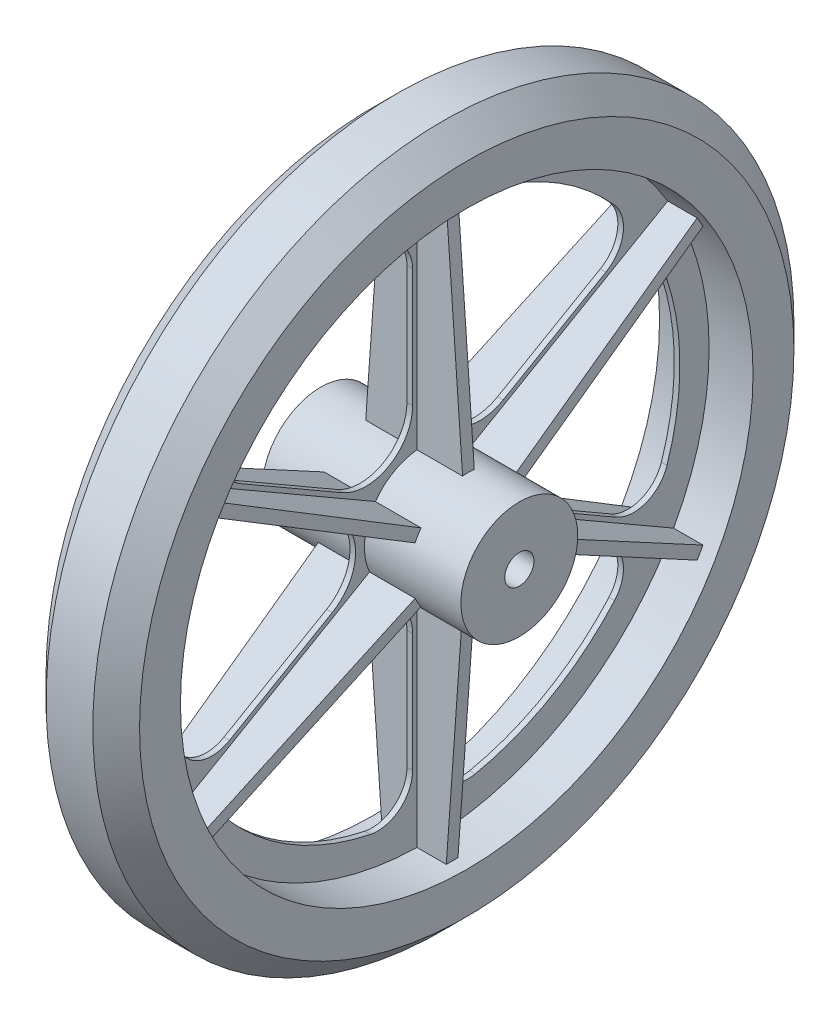
SolidWorks part; units mm, degrees
material "aluminio"
ref_plane "Alzado" through (0, 0, 0) normal (0, 0, 1) x (1, 0, 0)
ref_plane "Planta" through (0, 0, 0) normal (0, 1, 0) x (1, 0, 0)
ref_plane "Vista lateral" through (0, 0, 0) normal (1, 0, 0) x (0, 0, -1)
sketch "Croquis5" plane through (0, 0, 0) normal (1, 0, 0) x (0, 0, -1)
  circle A0 centre (0, 0) radius 15.875
  dimension "D1" = 31.75
extrude "Saliente-Extruir4" add sketch "Croquis5" along normal blind 26.9875 and the other way blind 26.9875
sketch "Croquis6" plane through (0, 0, 0) normal (1, 0, 0) x (0, 0, -1)
  circle A0 centre (0, 0) radius 95.25
  dimension "D1" = 190.5
extrude "Saliente-Extruir5" add sketch "Croquis6" along normal blind 0.762 and the other way blind 0.762
sketch "Croquis8" plane through (0, 0, 0) normal (1, 0, 0) x (0, 0, -1)
  circle A0 centre (0, 0) radius 95.25 construction
  circle A1 centre (0, 0) radius 95.25
  circle A2 centre (0, 0) radius 77.787
  dimension "D1" = 17.463
extrude "Saliente-Extruir6" add sketch "Croquis8" along normal blind 12.7 and the other way blind 12.7
sketch "Croquis9" plane through (0.762, 0, 0) normal (1, 0, 0) x (0, 0, -1)
  line L0 (0, 0) -> (0, 95.25) construction
  line L1 (0, 0) -> (82.4889, 47.625) construction
  line L2 (2.778, 26.8087) -> (2.778, 59.0571)
  line L3 (21.828, 15.8102) -> (49.756, 31.9344)
  circle A0 centre (0, 0) radius 95.25 construction
  circle A1 centre (0, 0) radius 95.25 construction
  arc A2 (52.0977, 46.528) -> (14.2456, 68.3819) centre (0, 0) ccw
  arc A3 (2.778, 59.0571) -> (14.2456, 68.3819) centre (12.303, 59.0571) cw
  arc A4 (2.778, 26.8087) -> (21.828, 15.8102) centre (15.478, 26.8087) ccw
  arc A5 (49.756, 31.9344) -> (52.0977, 46.528) centre (44.9935, 40.1833) ccw
  circle A6 centre (0, 0) radius 69.85 construction
  dimension "D5" = 9.525
  dimension "D6" = 9.525
  dimension "D7" = 12.7
  dimension "D2" = 60
  dimension "D3" = 5.556
  dimension "D4" = 5.556
  dimension "D1" = 25.4
extrude "Cortar-Extruir1" cut sketch "Croquis9" against normal through all
ref_plane "Plano1" through (0, 88.9, 0) normal (0, 1, 0) x (1, 0, 0)
sketch "Croquis10" plane through (0, 0, 0) normal (0, 1, 0) x (1, 0, 0)
  line L0 (26.9875, -15.875) -> (26.9875, 15.875) construction
  line L1 (-14.2875, 1.5875) -> (14.2875, 1.5875)
  line L2 (-14.2875, 1.5875) -> (-14.2875, -1.5875)
  line L3 (-14.2875, -1.5875) -> (14.2875, -1.5875)
  line L4 (14.2875, 1.5875) -> (14.2875, -1.5875)
  line L5 (-14.2875, 1.5875) -> (14.2875, -1.5875) construction
  line L6 (-14.2875, -1.5875) -> (14.2875, 1.5875) construction
  point P0 (0, 0)
  dimension "D1" = 12.7
  dimension "D2" = 3.175
sketch "Croquis11" plane through (0, 88.9, 0) normal (0, 1, 0) x (1, 0, 0)
  line L1 (-7.9375, 1.5875) -> (7.9375, 1.5875)
  line L2 (-7.9375, 1.5875) -> (-7.9375, -1.5875)
  line L3 (-7.9375, -1.5875) -> (7.9375, -1.5875)
  line L4 (7.9375, 1.5875) -> (7.9375, -1.5875)
  line L5 (-7.9375, 1.5875) -> (7.9375, -1.5875) construction
  line L6 (-7.9375, -1.5875) -> (7.9375, 1.5875) construction
  point P0 (0, 0)
  dimension "D1" = 15.875
  dimension "D2" = 3.175
loft "Recubrir1" add profiles "Croquis11", "Croquis10"
pattern_circular "MatrizC1" count 6 over 360 about axis through (-12.7, 0, 0) along (1, 0, 0) of "Recubrir1", "Cortar-Extruir1"
sketch "Croquis12" plane through (-26.9875, 0, 0) normal (-1, 0, 0) x (0, 0, 1)
  circle A0 centre (0, 0) radius 3.969
  dimension "D1" = 7.938
extrude "Cortar-Extruir2" cut sketch "Croquis12" against normal through all
chamfer "Chaflán1" distance 6.35 angle 45 2 edges at (12.7, 0, -95.25) (-12.7, 0, -95.25)
